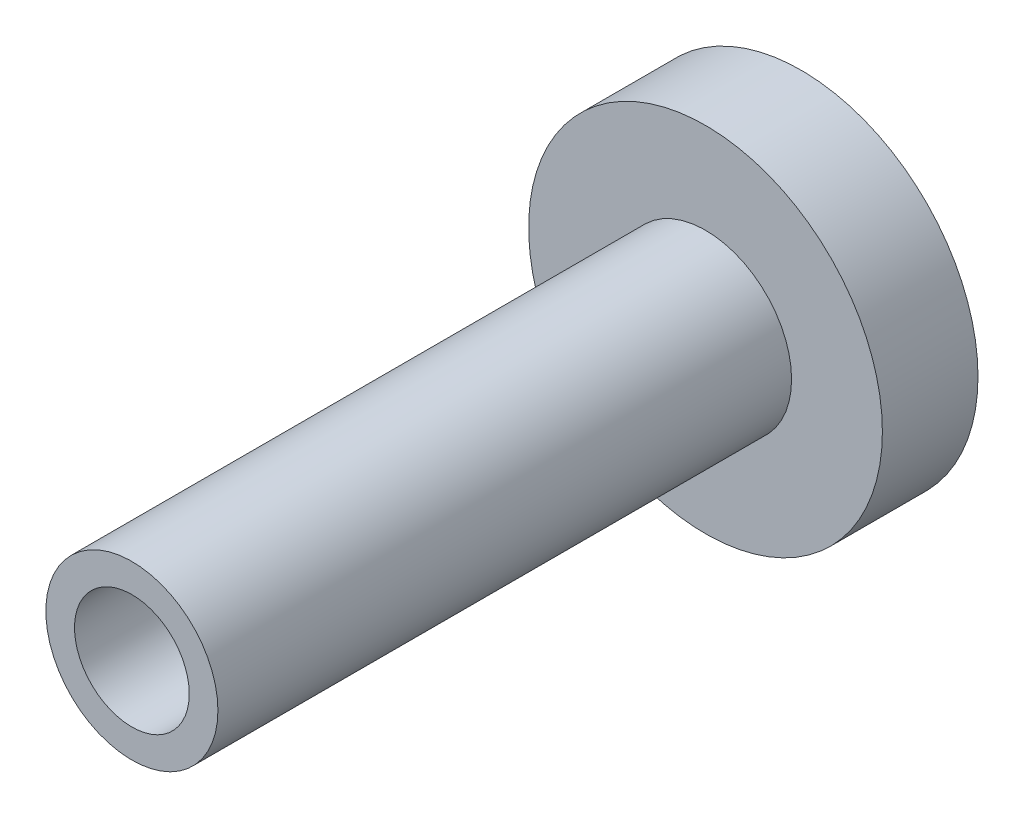
SolidWorks part; units mm, degrees
note: The reader was unsure of these and kept them because the rebuilt part matched: shared geometry of "Croquis1<6>".
ref_plane "Alzado" through (0, 0, 0) normal (0, 0, 1) x (1, 0, 0)
ref_plane "Planta" through (0, 0, 0) normal (0, 1, 0) x (1, 0, 0)
ref_plane "Vista lateral" through (0, 0, 0) normal (1, 0, 0) x (0, 0, -1)
sketch "Croquis1" plane through (0, 0, 0) normal (0, 0, 1) x (1, 0, 0)
  circle A0 centre (0, 0) radius 9.25
  circle A1 centre (0, 0) radius 3
  dimension "D1" = 18.5
  dimension "D2" = 6
extrude "Saliente-Extruir1" add sketch "Croquis1" along normal blind 5
extrude "Extruir-Lámina1" add sketch "Croquis1<6>" along normal blind 35 thin contours A1
sketch "Croquis1<6>" plane through (0, 0, 0) normal (0, 0, 1) x (1, 0, 0) same geometry as "Croquis1"
